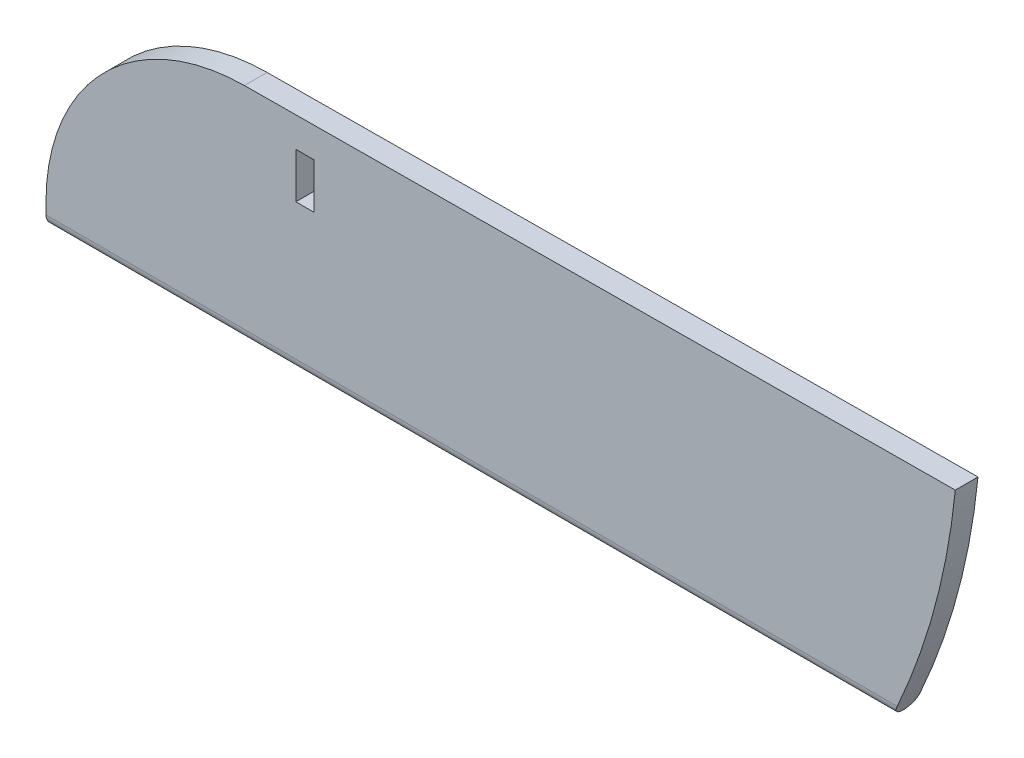
SolidWorks part; units mm, degrees
material "Papier ondulé"
ref_plane "Plan de face" through (0, 0, 0) normal (0, 0, 1) x (1, 0, 0)
ref_plane "Plan de dessus" through (0, 0, 0) normal (0, 1, 0) x (1, 0, 0)
ref_plane "Plan de droite" through (0, 0, 0) normal (1, 0, 0) x (0, 0, -1)
sketch "Esquisse1" plane through (0, 0, 0) normal (0, 0, 1) x (1, 0, 0)
  line L0 (0, 0) -> (188.5, 0) construction
  line L1 (0, 0) -> (0, -25)
  line L2 (0, -25) -> (37.5, -25)
  line L3 (37.5, -25) -> (37.5, -95.5)
  line L4 (37.5, -95.5) -> (32.5, -95.5)
  line L5 (32.5, -95.5) -> (36.4874, -115.0985)
  line L6 (36.4874, -115.0985) -> (88.4874, -115.0985)
  line L7 (88.4874, -115.0985) -> (159.198, -44.3878)
  line L8 (43.6829, 43.9989) -> (200.1829, 45.1267)
  arc A0 (0, 0) -> (43.6829, 43.9989) centre (44, 0) cw
  arc A1 (159.198, -44.3878) -> (200.1829, 45.1267) centre (49.0805, 60.1702) ccw
  dimension "D11" = 44
  dimension "D1" = 188.5
  dimension "D2" = 25
  dimension "D3" = 37.5
  dimension "D4" = 90
  dimension "D5" = 70.5
  dimension "D6" = 5
  dimension "D7" = 20
  dimension "D8" = 52
  dimension "D9" = 135
  dimension "D10" = 100
  dimension "D12" = 156.5
extrude "Boss.-Extru.1" add sketch "Esquisse1" along normal blind 5
sketch "Esquisse2" plane through (0, 0, 5) normal (0, 0, 1) x (1, 0, 0)
  line L0 (0, 0) -> (188.5, 0) construction
  line L2 (0, -5) -> (186.234, -5)
  line L3 (0, 0) -> (0, -25) construction
  line L5 (0, -5) -> (203.4249, -5)
  line L6 (0, -5) -> (0, -136.5496)
  line L7 (0, -136.5496) -> (203.4249, -136.5496)
  line L8 (203.4249, -5) -> (203.4249, -136.5496)
  arc A2 (159.198, -44.3878) -> (200.1829, 45.1267) centre (49.0805, 60.1702) ccw construction
  dimension "D1" = 188.5
  dimension "D2" = 5
sketch "Esquisse3" plane through (0, 0, 5) normal (0, 0, 1) x (1, 0, 0)
  line L1 (0, -25) -> (10, -25)
  line L2 (0, -25) -> (0, -22)
  line L3 (0, -22) -> (10, -22)
  line L4 (10, -25) -> (10, -22)
  dimension "D1" = 10
  dimension "D2" = 3
extrude "Enlèv. mat.-Extru.1" cut sketch "Esquisse3" against normal through all
sketch "Esquisse4" plane through (0, 0, 5) normal (0, 0, 1) x (1, 0, 0)
  line L0 (88.4874, -115.0985) -> (88.4874, -105.0985) construction
  line L1 (88.4874, -105.0985) -> (78.4874, -105.0985)
  line L2 (78.4874, -105.0985) -> (78.4874, -115.0985) construction
  line L3 (36.4874, -115.0985) -> (88.4874, -115.0985) construction
  line L4 (78.4874, -115.0985) -> (88.4874, -115.0985)
  line L5 (88.4874, -105.0985) -> (98.4874, -105.0985)
  line L6 (88.4874, -115.0985) -> (159.198, -44.3878) construction
  line L7 (98.4874, -105.0985) -> (88.4874, -115.0985)
  line L8 (78.4874, -105.0985) -> (78.4874, -111.0985)
  line L9 (78.4874, -111.0985) -> (68.4874, -115.0985)
  line L10 (68.4874, -115.0985) -> (78.4874, -115.0985)
  dimension "D1" = 10
  dimension "D2" = 10
  dimension "D3" = 10
  dimension "D4" = 4
extrude "Enlèv. mat.-Extru.2" cut sketch "Esquisse4" against normal through all
extrude "Enlèv. mat.-Extru.3" cut sketch "Esquisse2" against normal through all contours L6 L7 L8 L5
fillet "Congé1" radius 2.5 2 edges at (93.117, -5, 0) (93.117, -5, 5)
sketch "Esquisse5" plane through (0, 0, 5) normal (0, 0, 1) x (1, 0, 0)
  line L0 (187.3943, -2.5) -> (59, -2.5) construction
  line L1 (0, -2.5) -> (187.3943, -2.5) construction
  line L2 (59, -2.5) -> (59, 27.5) construction
  line L4 (59, 27.5) -> (55, 27.5)
  line L5 (59, 27.5) -> (59, 37.5)
  line L6 (59, 37.5) -> (55, 37.5)
  line L7 (55, 27.5) -> (55, 37.5)
  dimension "D1" = 55
  dimension "D2" = 30
  dimension "D3" = 4
  dimension "D4" = 10
extrude "Enlèv. mat.-Extru.4" cut sketch "Esquisse5" against normal through all
